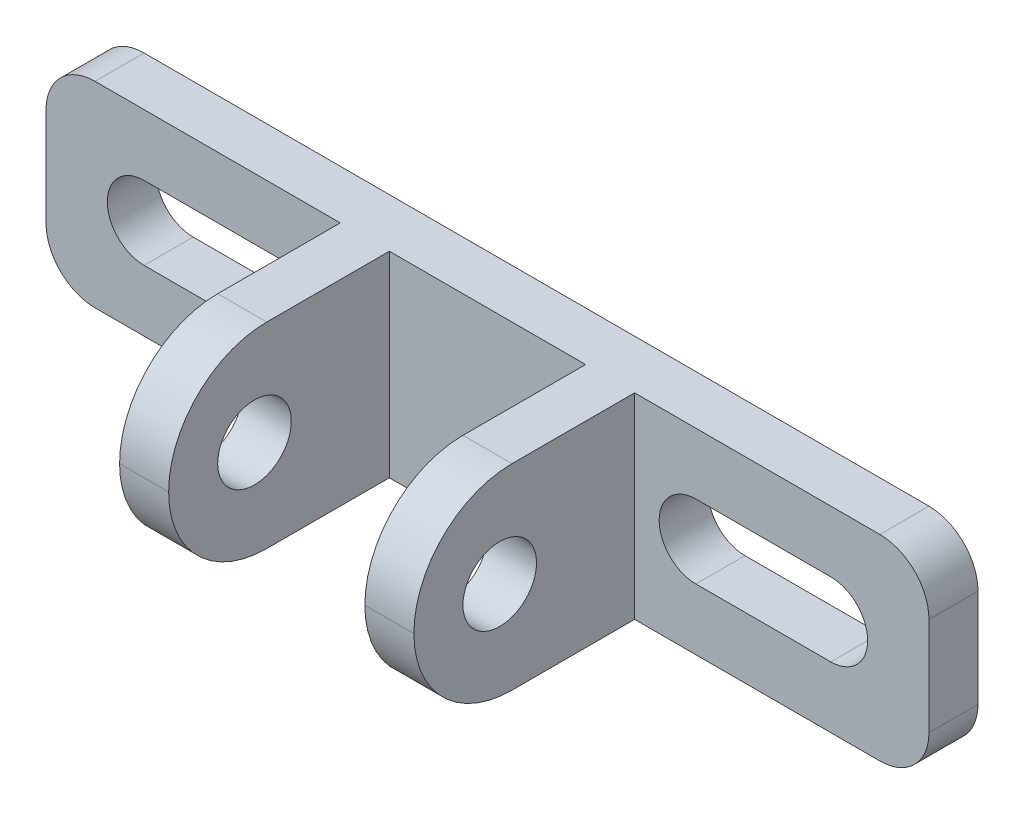
SolidWorks part; units mm, degrees
material "ABS"
ref_plane "前视基准面" through (0, 0, 0) normal (0, 0, 1) x (1, 0, 0)
ref_plane "上视基准面" through (0, 0, 0) normal (0, 1, 0) x (1, 0, 0)
ref_plane "右视基准面" through (0, 0, 0) normal (1, 0, 0) x (0, 0, -1)
sketch "草图1" plane through (0, 0, 0) normal (0, 0, 1) x (1, 0, 0)
  line L0 (0, 0) -> (-10.0532, 0) construction
  line L1 (0, 0) -> (0, 9.5745) construction
  line L3 (0, 0) -> (36, 0)
  line L4 (0, 0) -> (0, -8)
  line L5 (0, -8) -> (36, -8)
  line L6 (36, 0) -> (36, -8)
  dimension "D1" = 36
  dimension "D2" = 8
extrude "凸台-拉伸1" add sketch "草图1" along normal blind 11 contours L4 L3 L6 L5
sketch "草图2" plane through (0, 0, 11) normal (0, 0, 1) x (1, 0, 0)
  line L1 (0, 0) -> (36, 0) construction
  line L2 (0, -8) -> (36, -8) construction
  line L4 (14, -8) -> (22, -8)
  line L5 (22, -8) -> (22, 0)
  line L6 (22, 0) -> (14, 0)
  line L7 (14, 0) -> (14, -8)
  line L8 (12, 0) -> (12, -8)
  line L9 (12, -8) -> (0, -8)
  line L10 (0, -8) -> (0, 0)
  line L11 (0, 0) -> (12, 0)
  line L12 (24, 0) -> (24, -8)
  line L13 (24, -8) -> (36, -8)
  line L14 (36, -8) -> (36, 0)
  line L15 (36, 0) -> (24, 0)
  point P9 (18, 0)
  point P12 (18, -8)
  point P13 (18, 0)
extrude "切除-拉伸1" cut sketch "草图2" against normal blind 9
fillet "圆角1" radius 4 4 edges at (23, -8, 11) (23, 0, 11) (13, 0, 11) (13, -8, 11)
sketch "草图3" plane through (12, 0, 0) normal (-1, 0, 0) x (0, 0, 1)
  circle A0 centre (7.5, -4) radius 1.5
extrude "切除-拉伸2" cut sketch "草图3" against normal through all both and the other way through all
fillet "圆角2" radius 2 4 edges at (36, 0, 1) (36, -8, 1) (0, -8, 1) (0, 0, 1)
sketch "草图4" plane through (0, 0, 2) normal (0, 0, 1) x (1, 0, 0)
  line L0 (22, -4) -> (14, -4) construction
  line L2 (32, -4) -> (26.5, -4) construction
  line L7 (18, -4) -> (18, -8.6455) construction
  line L11 (4, -4) -> (9.5, -4) construction
  line L12 (32, -2.5) -> (26.5, -2.5)
  line L13 (4, -2.5) -> (9.5, -2.5)
  line L14 (4, -5.5) -> (9.5, -5.5)
  line L15 (32, -5.5) -> (26.5, -5.5)
  arc A4 (4, -2.5) -> (4, -5.5) centre (4, -4) ccw
  arc A5 (9.5, -5.5) -> (9.5, -2.5) centre (9.5, -4) ccw
  arc A6 (32, -2.5) -> (32, -5.5) centre (32, -4) cw
  arc A7 (26.5, -5.5) -> (26.5, -2.5) centre (26.5, -4) cw
  point P4 (29.25, -4)
  point P8 (6.75, -4)
  dimension "D1" = 3
  dimension "D2" = 5.5
extrude "切除-拉伸3" cut sketch "草图4" against normal blind 9
